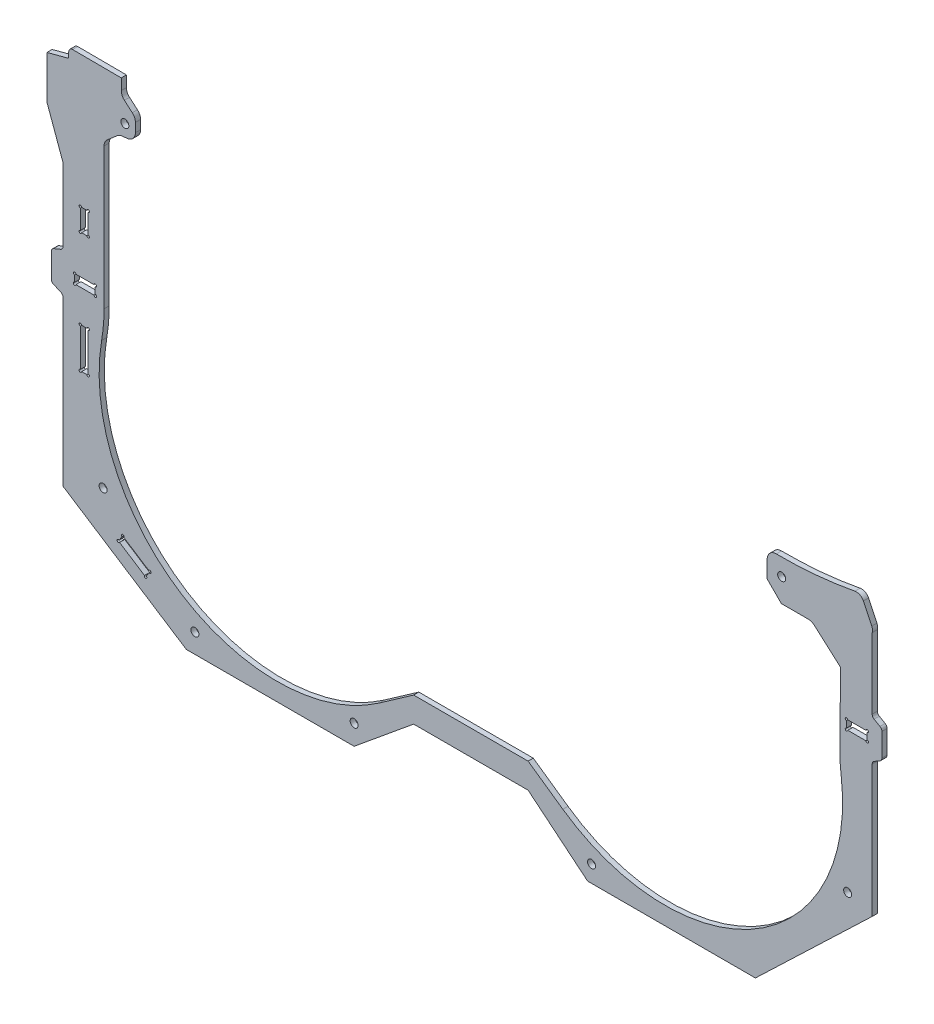
SolidWorks part; units mm, degrees
material "PPS"
ref_plane "前视基准面" through (0, 0, 0) normal (0, 0, 1) x (1, 0, 0)
ref_plane "上视基准面" through (0, 0, 0) normal (0, 1, 0) x (1, 0, 0)
ref_plane "右视基准面" through (0, 0, 0) normal (1, 0, 0) x (0, 0, -1)
sketch "草图1" plane through (0, 0, 0) normal (0, 0, 1) x (1, 0, 0)
  line L0 (-816.4831, 0) -> (39952.7477, 0) construction
  line L1 (0, 10.8762) -> (0, -592.6628) construction
  line L2 (0, 0) -> (206.9686, -284.8678) construction
  line L9 (155.1848, -135.6229) -> (110.024, -178.8146)
  line L10 (110.024, -178.8146) -> (45.146, -178.8146)
  line L60 (-110.024, -178.8146) -> (-45.146, -178.8146)
  line L119 (-135.8935, -19.3983) -> (-141.8504, -24.5203)
  line L187 (152.75, -77.5) -> (145.75, -77.5) construction
  line L188 (152.75, -77.5) -> (152.75, -75) construction
  line L189 (145.75, -77.5) -> (145.75, -75) construction
  line L190 (152.75, -75) -> (145.75, -75) construction
  line L191 (-145.75, -75) -> (-152.75, -75) construction
  line L192 (-152.75, -75) -> (-152.75, -77.5) construction
  line L193 (-152.75, -77.5) -> (-145.75, -77.5) construction
  line L194 (-145.75, -77.5) -> (-145.75, -75) construction
  line L195 (145.25, -74.5) -> (153.25, -74.5)
  line L196 (153.25, -74.5) -> (153.25, -78)
  line L197 (153.25, -78) -> (145.25, -78)
  line L198 (145.25, -78) -> (145.25, -74.5)
  line L199 (-153.25, -78) -> (-145.25, -78)
  line L200 (-153.25, -74.5) -> (-153.25, -78)
  line L201 (-145.25, -74.5) -> (-153.25, -74.5)
  line L202 (-145.25, -78) -> (-145.25, -74.5)
  line L204 (-135.1929, 0) -> (-155.5041, 0.108)
  line L205 (-155.5041, 3.8169) -> (-155.5041, -3.6009) construction
  line L206 (-155.5041, 0.108) -> (-155.5041, -3.6009)
  line L207 (-155.5041, -3.6009) -> (-163.9299, -5.8429)
  line L208 (-155.5041, -3.6009) -> (-170.0041, -7.4592) construction
  line L209 (-163.9299, -5.8429) -> (-163.9299, -22.4613)
  line L210 (-163.9299, -22.4613) -> (-157.7253, -39.5836)
  line L211 (-157.7253, -39.5836) -> (-157.7253, -148.0115)
  line L212 (-157.7253, -148.0115) -> (-110.024, -178.8146)
  line L215 (114.5778, -32.685) -> (114.5778, -42.9165)
  line L216 (120.0778, -48.4165) -> (131.782, -48.4165)
  line L217 (131.782, -48.4165) -> (142.9662, -58.3127)
  line L219 (151.7709, -31.6811) -> (155.0114, -38.4796)
  line L220 (155.1848, -40.6053) -> (155.1848, -135.6229)
  line L221 (120.1823, -39.335) -> (149.4323, -39.335) construction
  line L222 (92.9352, -48.4165) -> (142.5788, -48.4165) construction
  line L223 (75, -103.2286) -> (164.6276, -103.2286) construction
  line L224 (75, -103.2286) -> (35.5666, -159.5453) construction
  line L226 (35.5666, -159.5453) -> (22.126, -150.1341)
  line L227 (22.126, -150.1341) -> (-22.126, -150.1341)
  line L228 (22.126, -159.8702) -> (-22.126, -159.8702)
  line L229 (22.126, -159.8702) -> (45.146, -178.8146)
  line L230 (-35.5666, -159.5453) -> (-22.126, -150.1341)
  line L231 (-22.126, -159.8702) -> (-45.146, -178.8146)
  line L233 (114.5778, -42.9165) -> (120.0778, -48.4165)
  line L234 (75, -103.2286) -> (142.5988, -90.7) construction
  line L235 (142.9662, -58.3127) -> (142.5988, -90.7)
  line L236 (142.5988, -90.7) -> (142.5988, -57.1472) construction
  line L238 (-141.8504, -87.1793) -> (-75, -103.2286) construction
  line L239 (-75, -103.2286) -> (-143.75, -103.2286) construction
  line L240 (-141.8504, -24.5203) -> (-141.8504, -87.1793)
  line L241 (-135.1929, 0) -> (-135.1929, -5.85)
  line L242 (-135.1929, -5.85) -> (-129.7197, -10.5767)
  line L243 (-129.7197, -10.5767) -> (-129.7197, -18.7984)
  line L244 (-129.7197, -18.7984) -> (-135.8935, -19.3983)
  circle A76 centre (75, -103.2286) radius 68.75 construction
  circle A78 centre (-133.8062, -14.6009) radius 1.55
  arc A79 (155.0114, -38.4796) -> (155.1848, -40.6053) centre (152.3033, -39.7704) cw
  circle A80 centre (-75, -103.2286) radius 68.75 construction
  arc A81 (148.5011, -30.0249) -> (151.7709, -31.6811) centre (149.0628, -32.9719) cw
  arc A82 (153.902, -42.309) -> (155.0114, -38.4796) centre (152.3033, -39.7704) ccw construction
  arc A83 (148.5011, -30.0249) -> (114.5778, -32.685) centre (119.5082, 122.0773) cw
  arc A84 (97.7907, -31.2329) -> (148.5011, -30.0249) centre (119.5082, 122.0773) ccw construction
  circle A85 centre (149.4323, -39.335) radius 1.55 construction
  circle A86 centre (120.1823, -39.335) radius 1.55
  arc A87 (35.5666, -159.5453) -> (143.75, -103.2286) centre (75, -103.2286) ccw
  arc A88 (-35.5666, -159.5453) -> (-143.75, -103.2286) centre (-75, -103.2286) cw
  arc A89 (142.5988, -90.7) -> (143.75, -103.2286) centre (75, -103.2286) cw
  arc A91 (-143.75, -103.2286) -> (-141.8504, -87.1793) centre (-75, -103.2286) cw
  point P10 (149.25, -75)
  point P29 (0, -150.1341)
  point P32 (143.75, -58.3289)
  point P38 (153.25, -76.25)
  point P92 (0, -159.8702)
  point P93 (143.3081, -58.3457)
  point P94 (142.5988, -60.2347)
  point P95 (0, 0)
  dimension "D1" = 36
  dimension "D2" = 75
  dimension "D3" = 137.5
  dimension "D6" = 75
  dimension "D7" = 149.25
  dimension "D15" = 125
  dimension "D14" = 3.1
  dimension "D4" = 2.5
  dimension "D5" = 7
  dimension "D8" = 7
  dimension "D9" = 0.5
  dimension "D10" = 0.5
  dimension "D11" = 0.5
  dimension "D12" = 0.5
  dimension "D13" = 29.25
  dimension "D16" = 10.5
  dimension "D17" = 0.65
  dimension "D18" = 13.5
extrude "凸台-拉伸1" add sketch "草图1" along normal blind 2
sketch "草图2" plane through (0, 0, 0) normal (0, 0, 1) x (1, 0, 0)
  line L0 (155.1848, -68.75) -> (158.9348, -70.9151)
  line L1 (155.1848, -135.6229) -> (155.1848, -40.6053) construction
  line L2 (158.9348, -70.9151) -> (158.9348, -81.5849)
  line L3 (158.9348, -81.5849) -> (155.1848, -83.75)
  line L4 (155.1848, -83.75) -> (155.1848, -68.75)
  line L5 (153.25, -76.25) -> (184.2947, -76.25) construction
  line L6 (153.25, -78) -> (153.25, -74.5) construction
  line L7 (-153.25, -76.25) -> (-171.2105, -76.25) construction
  line L8 (-153.25, -74.5) -> (-153.25, -78) construction
  line L9 (-157.7253, -68.75) -> (-157.7253, -83.75)
  line L10 (-157.7253, -39.5836) -> (-157.7253, -148.0115) construction
  line L11 (-157.7253, -83.75) -> (-162.2253, -81.886)
  line L12 (-162.2253, -81.886) -> (-162.2253, -70.614)
  line L13 (-162.2253, -70.614) -> (-157.7253, -68.75)
  dimension "D1" = 3.75
  dimension "D2" = 7.5
  dimension "D3" = 60
  dimension "D4" = 67.5
  dimension "D5" = 4.5
extrude "凸台-拉伸2" add sketch "草图2" against normal up to surface from surface up to face at (-132.2562, -14.6009, 0) starting at face at (149.25, -76.25, 2)
fillet "圆角1" radius 66.25 2 edges at (-141.8504, -87.1793, 1) (142.5988, -90.7, 1)
fillet "圆角4" radius 1.5 9 edges at (155.1848, -68.75, 1) (158.9348, -70.9151, 1) (155.1848, -83.75, 1) (158.9348, -81.5849, 1) (-155.5041, 0.108, 1) (-157.7253, -68.75, 1) (-162.2253, -70.614, 1) (-162.2253, -81.886, 1) (-157.7253, -83.75, 1)
sketch "板状设备接口" plane through (0, 0, 2) normal (0, 0, 1) x (1, 0, 0)
  line L0 (-151, -90.5) -> (-148, -90.5)
  line L1 (-148, -90.5) -> (-148, -106)
  line L2 (-148, -106) -> (-151, -106)
  line L3 (-151, -106) -> (-151, -90.5)
  line L4 (-148, -77.5) -> (-148, -75) construction
  line L5 (-151, -75) -> (-151, -77.5) construction
  line L6 (-151, -51) -> (-148, -51)
  line L7 (-148, -51) -> (-148, -59.5)
  line L8 (-148, -59.5) -> (-151, -59.5)
  line L9 (-151, -59.5) -> (-151, -51)
  line L10 (-145.25, -74.5) -> (-153.25, -74.5) construction
  line L11 (-153.25, -78) -> (-145.25, -78) construction
  line L12 (-134.6497, -153.092) -> (-124.1488, -159.8729)
  line L13 (-124.1488, -159.8729) -> (-125.7762, -162.3931)
  line L14 (-125.7762, -162.3931) -> (-136.2771, -155.6122)
  line L15 (-136.2771, -155.6122) -> (-134.6497, -153.092)
  line L21 (-157.7253, -148.0115) -> (-110.024, -178.8146) construction
  line L22 (-131.0266, -159.0026) -> (-133.8746, -163.413) construction
  dimension "D1" = 15
  dimension "D2" = 8.5
  dimension "D3" = 12.5
  dimension "D4" = 15.5
  dimension "D5" = 5.25
  dimension "D6" = 12.5
  dimension "D7" = 3
extrude "设备接口" cut sketch "板状设备接口" against normal through all
sketch "草图4" plane through (0, 0, 0) normal (0, 0, 1) x (1, 0, 0)
  line L0 (-157.7253, -84.7523) -> (-157.7253, -148.0115) construction
  line L1 (-110.024, -178.8146) -> (-45.146, -178.8146) construction
  line L2 (155.1848, -135.6229) -> (155.1848, -84.616) construction
  line L3 (-45.146, -171.0646) -> (-45.146, -178.8146) construction
  line L4 (45.146, -178.8146) -> (110.024, -178.8146) construction
  circle A0 centre (-142.2253, -140.8215) radius 1.55
  circle A1 centre (-45.146, -171.0646) radius 1.55
  circle A2 centre (-106.713, -171.3146) radius 1.55
  circle A3 centre (46.656, -172.3146) radius 1.55
  circle A4 centre (145.6848, -132.301) radius 1.55
  dimension "D5" = 3.1
  dimension "D1" = 15.5
  dimension "D2" = 7.5
  dimension "D3" = 7.75
  dimension "D4" = 9.5
  dimension "D6" = 6.5
extrude "切除-拉伸3" cut sketch "草图4" along normal through all
fillet "圆角5" radius 3.5 7 edges at (131.782, -48.4165, 1) (114.5778, -32.685, 1) (-141.8504, -24.5203, 1) (-129.7197, -10.5767, 1) (-135.1929, -5.85, 1) (-135.8935, -19.3983, 1) (-129.7197, -18.7984, 1)
sketch "过切除" plane through (0, 0, 0) normal (0, 0, 1) x (1, 0, 0)
  circle A0 centre (-151, -51) radius 0.5
  circle A1 centre (-148, -51) radius 0.5
  circle A2 centre (-151, -59.5) radius 0.5
  circle A3 centre (-148, -59.5) radius 0.5
  circle A4 centre (-153.25, -74.5) radius 0.5
  circle A5 centre (-145.25, -74.5) radius 0.5
  circle A6 centre (-145.25, -78) radius 0.5
  circle A7 centre (-153.25, -78) radius 0.5
  circle A8 centre (-151, -90.5) radius 0.5
  circle A9 centre (-148, -90.5) radius 0.5
  circle A10 centre (-151, -106) radius 0.5
  circle A11 centre (-148, -106) radius 0.5
  circle A12 centre (-134.6497, -153.092) radius 0.5
  circle A13 centre (-136.2771, -155.6122) radius 0.5
  circle A14 centre (-124.1488, -159.8729) radius 0.5
  circle A15 centre (-125.7762, -162.3931) radius 0.5
  circle A16 centre (145.25, -74.5) radius 0.5
  circle A17 centre (153.25, -74.5) radius 0.5
  circle A18 centre (153.25, -78) radius 0.5
  circle A19 centre (145.25, -78) radius 0.5
  dimension "D1" = 1
extrude "这个是因为刀的限制不能切直角" cut sketch "过切除" along normal through all
